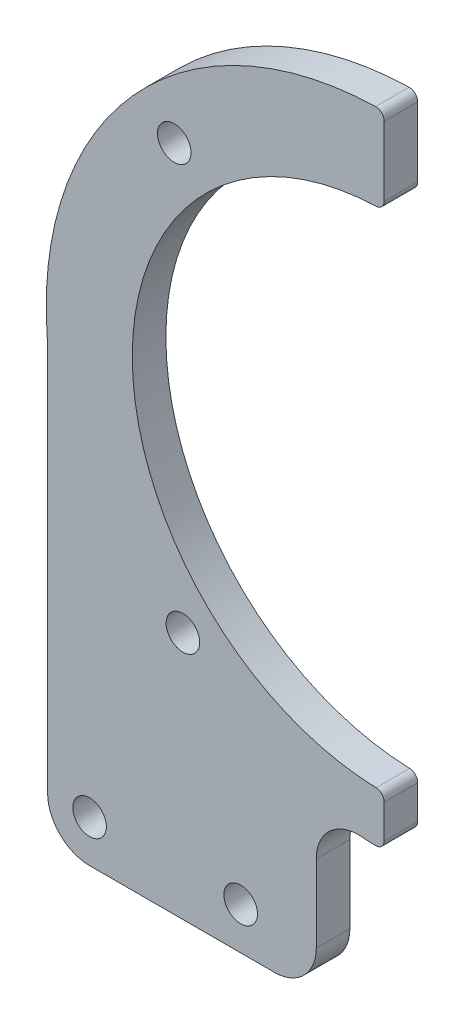
SolidWorks part; units mm, degrees
material "Acrylic (Medium-high impact)"
ref_plane "Front Plane" through (0, 0, 0) normal (0, 0, 1) x (1, 0, 0)
ref_plane "Top Plane" through (0, 0, 0) normal (0, 1, 0) x (1, 0, 0)
ref_plane "Right Plane" through (0, 0, 0) normal (1, 0, 0) x (0, 0, -1)
sketch "Sketch1" plane through (0, 0, 0) normal (0, 0, 1) x (1, 0, 0)
  line L0 (0, 0) -> (18, 0) construction
  line L1 (18, 0) -> (18, 36.0302) construction
  line L2 (0, 28.9286) -> (0, 0) construction
  line L3 (-5, -5) -> (-5, 46.4286)
  line L4 (-5, -5) -> (27, -5)
  line L5 (27, -5) -> (27, 15)
  line L9 (35.0863, 14.0801) -> (35.0863, 90.3323) construction
  line L10 (27, -5) -> (-5, 46.4286) construction
  line L11 (35.0863, 90.3323) -> (35.0863, 80.0801)
  line L12 (35.0863, 20.0801) -> (35.0863, 14.0801)
  line L14 (18, 0) -> (0, 28.9286) construction
  line L15 (-5, 46.4286) -> (-5, -5) construction
  circle A0 centre (0, 0) radius 2
  circle A1 centre (18, 0) radius 2
  arc A3 (35.0863, 80.0801) -> (35.0863, 20.0801) centre (35.0863, 50.0801) ccw
  arc A4 (35.0863, 90.3323) -> (-5, 46.4286) centre (35.0863, 50.0801) ccw
  arc A5 (27, 15) -> (35.0863, 14.0801) centre (35.0863, 50.0801) ccw
  dimension "D2" = 60
  dimension "D3" = 20
  dimension "D6" = 4
  dimension "D7" = 40.2522
  dimension "D4" = 18
  dimension "D5" = 32
  dimension "D1" = 5
extrude "Boss-Extrude1" add sketch "Sketch1" along normal blind 4
fillet "Fillet10" radius 1 4 edges at (35.0863, 90.3323, 2) (35.0863, 80.0801, 2) (35.0863, 14.0801, 2) (35.0863, 20.0801, 2)
fillet "Fillet11" radius 10 1 edges at (-5, 46.4286, 2)
fillet "Fillet12" radius 5 1 edges at (-5, -5, 2)
fillet "Fillet13" radius 5 1 edges at (27, -5, 2)
fillet "Fillet14" radius 5 1 edges at (27, 15, 2)
sketch "Sketch2" plane through (0, 0, 4) normal (0, 0, 1) x (1, 0, 0)
  line L1 (35.0863, 81.0639) -> (35.0863, 89.3196) construction
  circle A0 centre (10.0863, 74.575) radius 2
  circle A1 centre (11.1178, 24.575) radius 2
  arc A4 (33.9572, 85.0619) -> (33.9572, 15.0983) centre (35.0863, 50.0801) ccw construction
  dimension "D1" = 35
  dimension "D2" = 4
  dimension "D3" = 50
  dimension "D4" = 25
extrude "Cut-Extrude1" cut sketch "Sketch2" against normal blind 20
